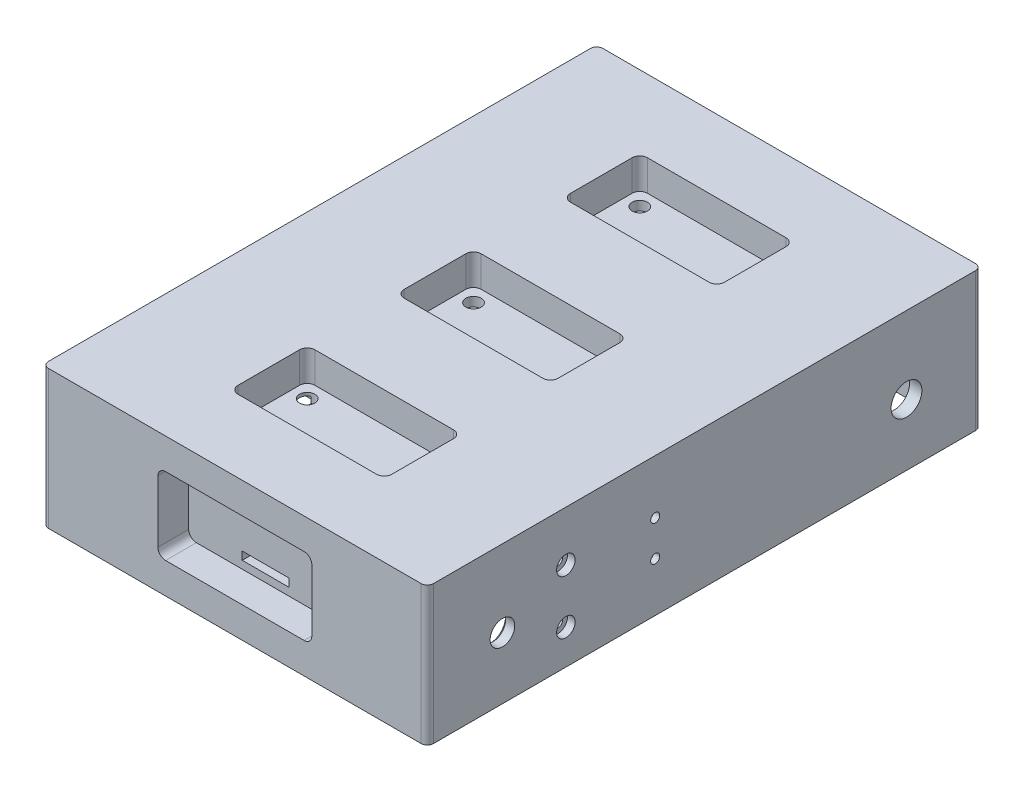
SolidWorks part; units mm, degrees
ref_plane "Спереди" through (0, 0, 0) normal (0, 0, 1) x (1, 0, 0)
ref_plane "Сверху" through (0, 0, 0) normal (0, 1, 0) x (1, 0, 0)
ref_plane "Справа" through (0, 0, 0) normal (1, 0, 0) x (0, 0, -1)
sketch "Эскиз1" plane through (0, 0, 0) normal (0, 1, 0) x (1, 0, 0)
  line L1 (-62.5, -90) -> (62.5, -90)
  line L2 (-62.5, -90) -> (-62.5, 90)
  line L3 (-62.5, 90) -> (62.5, 90)
  line L4 (62.5, -90) -> (62.5, 90)
  line L5 (-62.5, -90) -> (62.5, 90) construction
  line L6 (-62.5, 90) -> (62.5, -90) construction
  point P0 (0, 0)
  dimension "D1" = 125
  dimension "D2" = 180
extrude "Бобышка-Вытянуть1" add sketch "Эскиз1" along normal blind 45
sketch "Эскиз2" plane through (0, 0, 90) normal (0, 0, 1) x (1, 0, 0)
  line L0 (-1050, 22.5) -> (48950, 22.5) construction
  line L1 (-62.5, 45) -> (-62.5, 0) construction
  line L2 (0, -999.2777) -> (0, 49000.7223) construction
  line L4 (-22.5, 10) -> (22.5, 10)
  line L5 (-25, 12.5) -> (-25, 32.5)
  line L6 (-22.5, 35) -> (22.5, 35)
  line L7 (25, 12.5) -> (25, 32.5)
  line L8 (-25, 10) -> (25, 35) construction
  line L9 (-25, 35) -> (25, 10) construction
  arc A0 (-22.5, 35) -> (-25, 32.5) centre (-22.5, 32.5) ccw
  arc A1 (-25, 12.5) -> (-22.5, 10) centre (-22.5, 12.5) ccw
  arc A2 (25, 12.5) -> (22.5, 10) centre (22.5, 12.5) cw
  arc A3 (25, 32.5) -> (22.5, 35) centre (22.5, 32.5) ccw
  point P5 (-62.5, 22.5)
  point P6 (0, 22.5)
  dimension "D3" = 2.5
  dimension "D4" = 2.5
  dimension "D1" = 25
  dimension "D2" = 50
extrude "Вырез-Вытянуть1" cut sketch "Эскиз2" against normal blind 10
sketch "Эскиз4" plane through (0, 45, 0) normal (0, 1, 0) x (1, 0, 0)
  line L0 (0, -1000) -> (0, 49000) construction
  line L1 (-1000, 0) -> (49000, 0) construction
  line L2 (-22.5, 41.5) -> (22.5, 41.5)
  line L3 (-25, 44) -> (-25, 64)
  line L4 (-22.5, 66.5) -> (22.5, 66.5)
  line L5 (-22.5, -12.5) -> (22.5, -12.5)
  line L6 (-25, -10) -> (-25, 10)
  line L7 (-22.5, 12.5) -> (22.5, 12.5)
  line L8 (25, -10) -> (25, 10)
  line L9 (-25, -12.5) -> (25, 12.5) construction
  line L10 (-25, 12.5) -> (25, -12.5) construction
  line L11 (25, 44) -> (25, 64)
  line L12 (-25, 41.5) -> (25, 66.5) construction
  line L13 (-25, 66.5) -> (25, 41.5) construction
  line L14 (-25, -12.5) -> (25, -12.5) [skipped]
  line L15 (-25, -12.5) -> (-25, 12.5) [skipped]
  line L16 (-25, 12.5) -> (25, 12.5) [skipped]
  line L17 (25, -12.5) -> (25, 12.5) [skipped]
  line L18 (-25, -12.5) -> (25, 12.5) construction
  line L19 (-25, 12.5) -> (25, -12.5) construction
  line L20 (-22.5, -66.5) -> (22.5, -66.5)
  line L21 (-25, -64) -> (-25, -44)
  line L22 (-22.5, -41.5) -> (22.5, -41.5)
  line L23 (25, -64) -> (25, -44)
  line L24 (-25, -66.5) -> (25, -41.5) construction
  line L25 (-25, -41.5) -> (25, -66.5) construction
  arc A0 (22.5, -41.5) -> (25, -44) centre (22.5, -44) cw
  arc A1 (25, -64) -> (22.5, -66.5) centre (22.5, -64) cw
  arc A2 (-22.5, -66.5) -> (-25, -64) centre (-22.5, -64) cw
  arc A3 (-25, -44) -> (-22.5, -41.5) centre (-22.5, -44) cw
  arc A4 (-25, 64) -> (-22.5, 66.5) centre (-22.5, 64) cw
  arc A5 (-22.5, 12.5) -> (-25, 10) centre (-22.5, 10) ccw
  arc A6 (25, -10) -> (22.5, -12.5) centre (22.5, -10) cw
  arc A7 (22.5, 66.5) -> (25, 64) centre (22.5, 64) cw
  arc A8 (25, 44) -> (22.5, 41.5) centre (22.5, 44) cw
  arc A9 (-22.5, 41.5) -> (-25, 44) centre (-22.5, 44) cw
  arc A10 (22.5, 12.5) -> (25, 10) centre (22.5, 10) cw
  arc A11 (-22.5, -12.5) -> (-25, -10) centre (-22.5, -10) cw
  point P8 (0, 0)
  point P9 (0, 54)
  point P18 (0, 0)
  point P23 (0, -54)
  dimension "D7" = 2.5
  dimension "D8" = 2.5
  dimension "D1" = 25
  dimension "D2" = 50
  dimension "D5" = 41.5
  dimension "D6" = 41.5
  dimension "D3" = 2
  dimension "D4" = 2
extrude "Вырез-Вытянуть2" cut sketch "Эскиз4" against normal blind 10
mirror "Зеркальное отражение1" about plane through (0, 0, 0) normal (0, 0, 1) of "Вырез-Вытянуть1"
shell "Оболочка1" thickness 4 removed face at (0, 0, 0)
sketch "Эскиз5" plane through (-62.5, 0, 0) normal (-1, 0, 0) x (0, 0, 1)
  line L0 (45, 28.75) -> (45, 11.25) construction
  line L2 (90, 45) -> (90, 0) construction
  line L4 (-90, 0) -> (90, 0) construction
  line L7 (-1075, 20) -> (48925, 20) construction
  line L8 (-90, 45) -> (-90, 0) construction
  circle A3 centre (45, 28.75) radius 1.45
  circle A4 centre (45, 11.25) radius 1.45
  circle A5 centre (65.6, 20) radius 4
  circle A6 centre (-65.6, 20) radius 5
  dimension "D2" = 17.5
  dimension "D3" = 20
  dimension "D6" = 10
  dimension "D1" = 17.5
  dimension "D5" = 2.9
  dimension "D9" = 45
  dimension "D10" = 20.6
  dimension "D11" = 8
  dimension "D4" = 24.4
extrude "Вырез-Вытянуть3" cut sketch "Эскиз5" against normal blind 15
sketch "Эскиз6" plane through (-62.5, 0, 0) normal (-1, 0, 0) x (0, 0, 1)
  circle A2 centre (45, 28.75) radius 3
  circle A3 centre (45, 11.25) radius 3
  dimension "D1" = 6
extrude "Вырез-Вытянуть4" cut sketch "Эскиз6" against normal blind 2.5
sketch "Эскиз10" plane through (0, 31, 0) normal (0, -1, 0) x (-1, 0, 0)
  line L1 (21, -42) -> (26, -42)
  line L2 (21, -42) -> (21, -78.5)
  line L3 (21, -78.5) -> (26, -78.5)
  line L4 (26, -42) -> (26, -78.5)
  line L5 (21, -42) -> (26, -78.5) construction
  line L6 (21, -78.5) -> (26, -42) construction
  line L7 (29, -44) -> (29, -64) construction
  line L8 (22.5, -70.5) -> (-22.5, -70.5) construction
  point P4 (23.5, -60.25)
  dimension "D1" = 36.5
  dimension "D2" = 3
  dimension "D3" = 5
  dimension "D4" = 8
extrude "Вырез-Вытянуть15" cut sketch "Эскиз10" against normal blind 3 and the other way through all
sketch "Эскиз11" plane through (-58.5, 0, 0) normal (1, 0, 0) x (0, 0, -1)
  circle A1 centre (-65.6, 20) radius 5
  dimension "D1" = 10
extrude "Вырез-Вытянуть16" cut sketch "Эскиз11" against normal blind 1
mirror "Зеркальное отражение2" about plane through (0, 0, 0) normal (1, 0, 0) of "Вырез-Вытянуть16", "Вырез-Вытянуть15", "Вырез-Вытянуть4", "Вырез-Вытянуть3"
sketch "Эскиз12" plane through (0, 6, 0) normal (0, -1, 0) x (-1, 0, 0)
  line L0 (-1014.7864, -78) -> (48985.2136, -78) construction
  line L1 (21, -76) -> (-21, -76) construction
  line L2 (0, -1061) -> (0, 48939) construction
  line L3 (-10, -1061) -> (-10, 48939) construction
  line L4 (10, -1061) -> (10, 48939) construction
  circle A0 centre (-10, -78) radius 1.45
  circle A1 centre (10, -78) radius 1.45
  point P7 (0, -76)
  dimension "D4" = 2.9
  dimension "D1" = 2
  dimension "D2" = 20
  dimension "D3" = 10
extrude "Вырез-Вытянуть17" cut sketch "Эскиз12" against normal blind 14
sketch "Эскиз15" plane through (0, 35, 0) normal (0, 1, 0) x (1, 0, 0)
  line L0 (-1010.1672, -62.5) -> (48989.8328, -62.5) construction
  line L1 (0, -1031.5) -> (0, 48968.5) construction
  line L2 (-7.6, -63.8) -> (7.6, -63.8)
  line L3 (-7.6, -63.8) -> (-7.6, -61.2)
  line L4 (-7.6, -61.2) -> (7.6, -61.2)
  line L5 (7.6, -63.8) -> (7.6, -61.2)
  line L6 (-7.6, -63.8) -> (7.6, -61.2) construction
  line L7 (-7.6, -61.2) -> (7.6, -63.8) construction
  line L8 (22.5, -41.5) -> (-22.5, -41.5) construction
  line L9 (-22.5, -66.5) -> (22.5, -66.5) construction
  line L10 (-7.6, -9.8) -> (7.6, -9.8)
  line L11 (-7.6, -9.8) -> (-7.6, -7.2)
  line L12 (-7.6, -7.2) -> (7.6, -7.2)
  line L13 (7.6, -9.8) -> (7.6, -7.2)
  line L14 (-7.6, -9.8) -> (7.6, -7.2) construction
  line L15 (-7.6, -7.2) -> (7.6, -9.8) construction
  line L16 (-7.6, 44.2) -> (7.6, 44.2)
  line L17 (-7.6, 44.2) -> (-7.6, 46.8)
  line L18 (-7.6, 46.8) -> (7.6, 46.8)
  line L19 (7.6, 44.2) -> (7.6, 46.8)
  line L20 (-7.6, 44.2) -> (7.6, 46.8) construction
  line L21 (-7.6, 46.8) -> (7.6, 44.2) construction
  line L23 (22.5, 12.5) -> (-22.5, 12.5) construction
  line L24 (-7.6, -59.8) -> (7.6, -59.8)
  line L25 (-7.6, -59.8) -> (-7.6, -57.2)
  line L26 (-7.6, -57.2) -> (7.6, -57.2)
  line L27 (7.6, -59.8) -> (7.6, -57.2)
  line L28 (-7.6, -59.8) -> (7.6, -57.2) construction
  line L29 (-7.6, -57.2) -> (7.6, -59.8) construction
  line L30 (-7.6, -5.8) -> (7.6, -5.8)
  line L31 (-7.6, -5.8) -> (-7.6, -3.2)
  line L32 (-7.6, -3.2) -> (7.6, -3.2)
  line L33 (7.6, -5.8) -> (7.6, -3.2)
  line L34 (-7.6, -5.8) -> (7.6, -3.2) construction
  line L35 (-7.6, -3.2) -> (7.6, -5.8) construction
  line L36 (-7.6, 48.2) -> (7.6, 48.2)
  line L37 (-7.6, 48.2) -> (-7.6, 50.8)
  line L38 (-7.6, 50.8) -> (7.6, 50.8)
  line L39 (7.6, 48.2) -> (7.6, 50.8)
  line L40 (-7.6, 48.2) -> (7.6, 50.8) construction
  line L41 (-7.6, 50.8) -> (7.6, 48.2) construction
  line L42 (-22.5, -12.5) -> (22.5, -12.5) construction
  circle A0 centre (-20, -46.5) radius 2.5
  circle A1 centre (20, -46.5) radius 2.5
  circle A2 centre (-20, 7.5) radius 2.5
  circle A3 centre (20, 7.5) radius 2.5
  circle A4 centre (-20, 61.5) radius 2.5
  circle A5 centre (20, 61.5) radius 2.5
  point P1 (0, -62.5)
  point P12 (0, -41.5)
  point P16 (0, -8.5)
  point P21 (0, 45.5)
  point P41 (0, -4.5)
  point P42 (0, -58.5)
  point P51 (0, 49.5)
  dimension "D6" = 40
  dimension "D8" = 5
  dimension "D1" = 2.6
  dimension "D2" = 15.2
  dimension "D3" = 4
  dimension "D4" = 3
  dimension "D5" = 4
  dimension "D7" = 40
  dimension "D9" = 5
  dimension "D10" = 3
  dimension "D11" = 5
  dimension "D13" = 4
  dimension "D15" = 4
  dimension "D12" = 2
  dimension "D14" = 3
extrude "Вырез-Вытянуть20" cut sketch "Эскиз15" against normal blind 3
sketch "Эскиз16" plane through (0, 32, 0) normal (0, 1, 0) x (1, 0, 0)
  line L0 (-7.6, -62.5) -> (7.6, -62.5) construction
  line L1 (-7.6, -61.2) -> (-7.6, -63.8) construction
  line L2 (7.6, -63.8) -> (7.6, -61.2) construction
  line L3 (0, -1000) -> (0, 49000) construction
  line L4 (-7, -63.4) -> (7, -63.4)
  line L5 (-7, -63.4) -> (-7, -61.6)
  line L6 (-7, -61.6) -> (7, -61.6)
  line L7 (7, -63.4) -> (7, -61.6)
  line L8 (-7, -63.4) -> (7, -61.6) construction
  line L9 (-7, -61.6) -> (7, -63.4) construction
  line L10 (-7, -9.4) -> (7, -9.4)
  line L11 (-7, -9.4) -> (-7, -7.6)
  line L12 (-7, -7.6) -> (7, -7.6)
  line L13 (7, -9.4) -> (7, -7.6)
  line L14 (-7.6, -8.5) -> (7.6, -8.5) construction
  line L15 (-7, -9.4) -> (7, -7.6) construction
  line L16 (-7, -7.6) -> (7, -9.4) construction
  line L17 (-7, 44.6) -> (7, 44.6)
  line L18 (-7, 44.6) -> (-7, 46.4)
  line L19 (-7, 46.4) -> (7, 46.4)
  line L20 (7, 44.6) -> (7, 46.4)
  line L21 (-7.6, 45.5) -> (7.6, 45.5) construction
  line L22 (-7, 44.6) -> (7, 46.4) construction
  line L23 (-7, 46.4) -> (7, 44.6) construction
  line L24 (-7.6, -7.2) -> (-7.6, -9.8) construction
  line L25 (-7.6, -58.5) -> (7.6, -58.5) construction
  line L26 (-7, -59.4) -> (7, -59.4)
  line L27 (-7, -59.4) -> (-7, -57.6)
  line L28 (-7, -57.6) -> (7, -57.6)
  line L29 (7, -59.4) -> (7, -57.6)
  line L30 (-7, -59.4) -> (7, -57.6) construction
  line L31 (-7, -57.6) -> (7, -59.4) construction
  line L32 (-7.6, -57.2) -> (-7.6, -59.8) construction
  line L33 (7.6, -59.8) -> (7.6, -57.2) construction
  line L34 (-7.6, -4.5) -> (7.6, -4.5) construction
  line L35 (-7.6, -3.2) -> (-7.6, -5.8) construction
  line L36 (7.6, -5.8) -> (7.6, -3.2) construction
  line L37 (-7.6, -9.8) -> (7.6, -9.8) construction
  line L38 (-7, -5.4) -> (7, -5.4)
  line L39 (-7, -5.4) -> (-7, -3.6)
  line L40 (-7, -3.6) -> (7, -3.6)
  line L41 (7, -5.4) -> (7, -3.6)
  line L42 (-7, -5.4) -> (7, -3.6) construction
  line L43 (-7, -3.6) -> (7, -5.4) construction
  line L44 (7.6, -9.8) -> (7.6, -7.2) construction
  line L45 (-7.6, 46.8) -> (-7.6, 44.2) construction
  line L46 (7.6, 44.2) -> (7.6, 46.8) construction
  line L47 (-7.6, 44.2) -> (7.6, 44.2) construction
  line L48 (-7.6, 49.5) -> (7.6, 49.5) construction
  line L49 (-7.6, 50.8) -> (-7.6, 48.2) construction
  line L50 (7.6, 48.2) -> (7.6, 50.8) construction
  line L52 (-7, 48.6) -> (7, 48.6)
  line L53 (-7, 48.6) -> (-7, 50.4)
  line L54 (-7, 50.4) -> (7, 50.4)
  line L55 (7, 48.6) -> (7, 50.4)
  line L56 (-7, 48.6) -> (7, 50.4) construction
  line L57 (-7, 50.4) -> (7, 48.6) construction
  point P6 (0, -62.5)
  point P12 (0, -58.5)
  point P17 (0, -8.5)
  point P24 (0, 36.6)
  point P41 (0, -4.5)
  point P54 (0, 49.5)
  dimension "D1" = 1.8
  dimension "D2" = 14
  dimension "D4" = 0.4
  dimension "D3" = 0.4
extrude "Вырез-Вытянуть21" cut sketch "Эскиз16" against normal blind 3
sketch "Эскиз17" plane through (0, 0, 80) normal (0, 0, 1) x (1, 0, 0)
  line L0 (-7.6, 12.5) -> (7.6, 12.5)
  line L1 (-7.6, 12.5) -> (-7.6, 15.1)
  line L2 (-7.6, 15.1) -> (7.6, 15.1)
  line L3 (7.6, 12.5) -> (7.6, 15.1)
  line L4 (-7.6, 12.5) -> (7.6, 15.1) construction
  line L5 (-7.6, 15.1) -> (7.6, 12.5) construction
  line L8 (-22.5, 10) -> (22.5, 10) construction
  line L9 (0, -965) -> (0, 49035) construction
  line L10 (22.5, 35) -> (-22.5, 35) construction
  circle A0 centre (-20, 30) radius 2.5
  circle A1 centre (20, 30) radius 2.5
  point P0 (0, 13.8)
  point P20 (0, 35)
  dimension "D5" = 5
  dimension "D1" = 2.6
  dimension "D2" = 15.2
  dimension "D3" = 40
  dimension "D4" = 40
  dimension "D6" = 2.5
  dimension "D7" = 5
extrude "Вырез-Вытянуть22" cut sketch "Эскиз17" against normal blind 3
sketch "Эскиз18" plane through (0, 0, 77) normal (0, 0, 1) x (1, 0, 0)
  line L0 (-7.6, 13.8) -> (7.6, 13.8) construction
  line L1 (-7.6, 15.1) -> (-7.6, 12.5) construction
  line L2 (7.6, 12.5) -> (7.6, 15.1) construction
  line L4 (-7, 12.9) -> (7, 12.9)
  line L5 (-7, 12.9) -> (-7, 14.7)
  line L6 (-7, 14.7) -> (7, 14.7)
  line L7 (7, 12.9) -> (7, 14.7)
  line L8 (-7, 12.9) -> (7, 14.7) construction
  line L9 (-7, 14.7) -> (7, 12.9) construction
  point P6 (0, 13.8)
  dimension "D1" = 1.8
  dimension "D2" = 14
extrude "Вырез-Вытянуть23" cut sketch "Эскиз18" against normal blind 3
sketch "Эскиз19" plane through (0, 0, -80) normal (0, 0, -1) x (1, 0, 0)
  line L0 (-7.6, -32.5) -> (7.6, -32.5)
  line L1 (-7.6, -32.5) -> (-7.6, -29.9)
  line L2 (-7.6, -29.9) -> (7.6, -29.9)
  line L3 (7.6, -32.5) -> (7.6, -29.9)
  line L4 (-7.6, -32.5) -> (7.6, -29.9) construction
  line L5 (-7.6, -29.9) -> (7.6, -32.5) construction
  line L6 (0, -1010) -> (0, 48990) construction
  line L7 (-22.5, -10) -> (22.5, -10) construction
  line L10 (22.5, -35) -> (-22.5, -35) construction
  circle A0 centre (-20, -15) radius 2.5
  circle A1 centre (20, -15) radius 2.5
  point P0 (0, -31.2)
  point P14 (0, -10)
  dimension "D5" = 5
  dimension "D7" = 2.5
  dimension "D1" = 2.6
  dimension "D2" = 15.2
  dimension "D3" = 40
  dimension "D4" = 40
  dimension "D6" = 5
extrude "Вырез-Вытянуть24" cut sketch "Эскиз19" against normal blind 3
sketch "Эскиз20" plane through (0, 0, -77) normal (0, 0, -1) x (1, 0, 0)
  line L0 (-1007.6, -31.2) -> (48992.4, -31.2) construction
  line L1 (-7.6, -29.9) -> (-7.6, -32.5) construction
  line L3 (-7, -32.1) -> (7, -32.1)
  line L4 (-7, -32.1) -> (-7, -30.3)
  line L5 (-7, -30.3) -> (7, -30.3)
  line L6 (7, -32.1) -> (7, -30.3)
  line L7 (-7, -32.1) -> (7, -30.3) construction
  line L8 (-7, -30.3) -> (7, -32.1) construction
  line L10 (0, -1029.9) -> (0, 48970.1) construction
  line L11 (7.6, -29.9) -> (-7.6, -29.9) construction
  point P1 (0, -31.2)
  point P5 (-7.6, -31.2)
  point P18 (0, -29.9)
  dimension "D1" = 1.8
  dimension "D2" = 14
extrude "Вырез-Вытянуть25" cut sketch "Эскиз20" against normal blind 5
sketch "Эскиз21" plane through (0, 0, -90) normal (0, 0, -1) x (1, 0, 0)
  line L0 (-975, -22.5) -> (49025, -22.5) construction
  line L1 (47.75, -29.75) -> (57.25, -29.75)
  line L2 (47.75, -29.75) -> (47.75, -15.25)
  line L3 (47.75, -15.25) -> (57.25, -15.25)
  line L4 (57.25, -29.75) -> (57.25, -15.25)
  line L5 (47.75, -29.75) -> (57.25, -15.25) construction
  line L6 (47.75, -15.25) -> (57.25, -29.75) construction
  line L7 (25, -12.5) -> (25, -32.5) construction
  line L8 (52.5, -1022.5) -> (52.5, 48977.5) construction
  line L9 (62.5, -45) -> (62.5, 0) construction
  point P0 (52.5, -22.5)
  point P10 (25, -22.5)
  dimension "D1" = 9.5
  dimension "D2" = 14.5
  dimension "D3" = 10
extrude "Вырез-Вытянуть26" cut sketch "Эскиз21" against normal blind 4
sketch "Эскиз22" plane through (0, 0, 0) normal (0, -1, 0) x (-1, 0, 0)
  line L0 (-60.5, -925) -> (-60.5, 49075) construction
  line L2 (-62.5, -90) -> (-62.5, 90) construction
  line L3 (-1046.2998, 88) -> (48953.7002, 88) construction
  line L4 (-62.5, 90) -> (62.5, 90) construction
  line L5 (60.5, -925) -> (60.5, 49075) construction
  line L6 (62.5, 90) -> (62.5, -90) construction
  line L7 (-1052.5, -88) -> (48947.5, -88) construction
  line L8 (62.5, -90) -> (-62.5, -90) construction
  line L9 (0, -925) -> (0, 49075) construction
  line L10 (-1052.5, 0) -> (48947.5, 0) construction
  circle A0 centre (-60.5, -88) radius 1.425
  circle A1 centre (-60.5, 88) radius 1.425
  circle A2 centre (60.5, 88) radius 1.425
  circle A3 centre (60.5, -88) radius 1.425
  circle A4 centre (0, 88) radius 1.425
  circle A5 centre (0, -88) radius 1.425
  circle A6 centre (-60.5, 0) radius 1.425
  circle A7 centre (60.5, 0) radius 1.425
  point P27 (0, 90)
  point P34 (-62.5, 0)
  dimension "D5" = 2.85
  dimension "D1" = 2
  dimension "D2" = 2
  dimension "D3" = 2
  dimension "D4" = 2
extrude "Вырез-Вытянуть27" cut sketch "Эскиз22" against normal blind 9
sketch "Эскиз24" plane through (-62.5, 0, 0) normal (-1, 0, 0) x (0, 0, 1)
  line L0 (0, -1000) -> (0, 49000) construction
  line L1 (16, -988.2808) -> (16, 49011.7192) construction
  line L2 (-90, 0) -> (90, 0) construction
  circle A0 centre (16, 16) radius 1.475
  circle A1 centre (16, 27.5) radius 1.475
  dimension "D4" = 2.95
  dimension "D1" = 11.5
  dimension "D2" = 16
  dimension "D3" = 16
extrude "Вырез-Вытянуть28" cut sketch "Эскиз24" against normal through all
fillet "Скругление1" radius 2 4 edges at (62.5, 22.5, -90) (-62.5, 22.5, -90) (62.5, 22.5, 90) (-62.5, 22.5, 90)
sketch "Эскиз26" plane through (58.5, 0, 0) normal (-1, 0, 0) x (0, 0, 1)
  line L1 (17.6454, 18.85) -> (14.3546, 18.85)
  line L2 (14.3546, 18.85) -> (12.7091, 16)
  line L3 (12.7091, 16) -> (14.3546, 13.15)
  line L4 (14.3546, 13.15) -> (17.6454, 13.15)
  line L5 (17.6454, 13.15) -> (19.2909, 16)
  line L6 (19.2909, 16) -> (17.6454, 18.85)
  line L7 (17.6454, 30.35) -> (14.3546, 30.35)
  line L8 (14.3546, 30.35) -> (12.7091, 27.5)
  line L9 (12.7091, 27.5) -> (14.3546, 24.65)
  line L10 (14.3546, 24.65) -> (17.6454, 24.65)
  line L11 (17.6454, 24.65) -> (19.2909, 27.5)
  line L12 (19.2909, 27.5) -> (17.6454, 30.35)
  circle A0 centre (16, 16) radius 2.85 construction
  circle A1 centre (16, 27.5) radius 2.85 construction
  dimension "D1" = 5.7
extrude "Вырез-Вытянуть29" cut sketch "Эскиз26" against normal blind 2 and the other way blind 119
